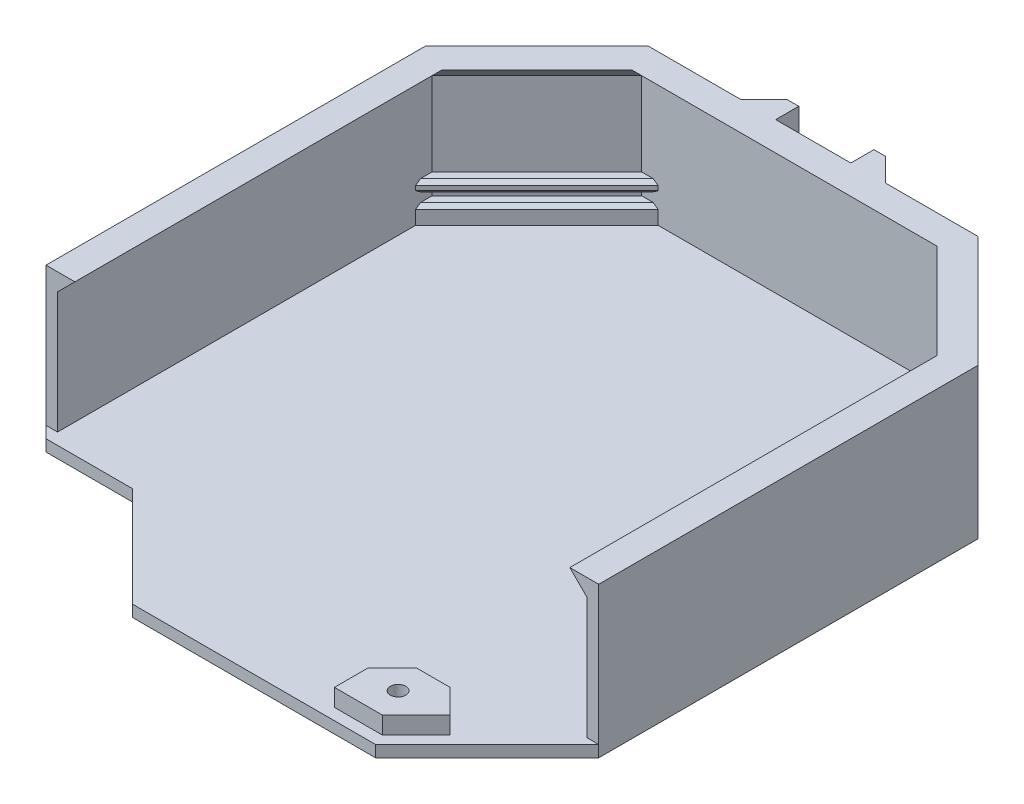
SolidWorks part; units mm, degrees
ref_plane "Front Plane" through (0, 0, 0) normal (0, 0, 1) x (1, 0, 0)
ref_plane "Top Plane" through (0, 0, 0) normal (0, 1, 0) x (1, 0, 0)
ref_plane "Right Plane" through (0, 0, 0) normal (1, 0, 0) x (0, 0, -1)
sketch "Sketch1" plane through (0, 0, 0) normal (0, 1, 0) x (1, 0, 0)
  line L2 (-1000, 0) -> (49000, 0) construction
  line L3 (0, -993.9005) -> (0, 49006.0995) construction
  line L6 (-36.195, 66.167) -> (36.195, 66.167)
  line L7 (36.195, 66.167) -> (60.706, 41.656)
  line L8 (60.706, 41.656) -> (60.706, -41.656)
  line L9 (-60.706, 41.656) -> (-60.706, -41.656)
  line L10 (-36.195, 66.167) -> (-60.706, 41.656)
  line L11 (-36.195, -66.167) -> (-60.706, -41.656)
  line L12 (-36.195, -66.167) -> (36.195, -66.167)
  line L13 (36.195, -66.167) -> (60.706, -41.656)
  point P13 (0, 66.167)
  point P14 (-60.706, 0)
  point P17 (60.706, 0)
  dimension "D1" = 132.334
  dimension "D2" = 121.412
  dimension "D3" = 135
  dimension "D4" = 41.656
extrude "Boss-Extrude1" add sketch "Sketch1" along normal blind 2.54
sketch "Sketch5" plane through (0, 2.54, 0) normal (0, 1, 0) x (1, 0, 0)
  line L0 (60.706, -41.656) -> (60.706, 41.656) construction
  line L1 (60.706, 41.656) -> (36.195, 66.167) construction
  line L2 (36.195, 66.167) -> (-36.195, 66.167) construction
  line L3 (-36.195, 66.167) -> (-60.706, 41.656) construction
  line L4 (-60.706, 41.656) -> (-60.706, -41.656) construction
  line L5 (60.706, -41.656) -> (60.706, 41.656)
  line L6 (60.706, 41.656) -> (36.195, 66.167)
  line L7 (36.195, 66.167) -> (-36.195, 66.167)
  line L8 (-36.195, 66.167) -> (-60.706, 41.656)
  line L9 (-60.706, 41.656) -> (-60.706, -41.656)
  line L10 (58.166, -41.656) -> (58.166, 40.6039)
  line L11 (58.166, 40.6039) -> (35.1429, 63.627)
  line L12 (35.1429, 63.627) -> (-35.1429, 63.627)
  line L13 (-35.1429, 63.627) -> (-58.166, 40.6039)
  line L14 (-58.166, 40.6039) -> (-58.166, -41.656)
  line L15 (-60.706, -41.656) -> (-58.166, -41.656)
  line L16 (58.166, -41.656) -> (60.706, -41.656)
  dimension "D1" = 2.54
extrude "Boss-Extrude2" add sketch "Sketch5" along normal blind 30.48
sketch "Sketch8" plane through (0, 2.54, 0) normal (0, 1, 0) x (1, 0, 0)
  line L0 (-58.166, -44.196) -> (-36.195, -66.167)
  line L1 (-60.706, -41.656) -> (-36.195, -66.167) construction
  line L2 (-36.195, -66.167) -> (-17.145, -66.167)
  line L3 (-36.195, -66.167) -> (36.195, -66.167) construction
  line L4 (-17.145, -66.167) -> (-39.116, -44.196)
  line L5 (-39.116, -44.196) -> (-58.166, -44.196)
  line L6 (-60.706, -41.656) -> (-58.166, -41.656) construction
  dimension "D1" = 2.54
  dimension "D2" = 19.05
extrude "Cut-Extrude2" cut sketch "Sketch8" against normal through all
ref_plane "PCB Bottom" through (0, 6.35, 0) normal (0, 1, 0) x (1, 0, 0)
ref_plane "PCB Top (With Tolerance)" through (0, 8.35, 0) normal (0, 1, 0) x (1, 0, 0)
sketch "Sketch9" plane through (0, 6.35, 0) normal (0, 1, 0) x (1, 0, 0)
  line L0 (-58.166, 40.6039) -> (-35.1429, 63.627)
  line L1 (-35.1429, 63.627) -> (-31.5508, 63.627)
  line L2 (-35.1429, 63.627) -> (35.1429, 63.627) construction
  line L3 (-31.5508, 63.627) -> (-58.166, 37.0118)
  line L4 (-58.166, -41.656) -> (-58.166, 40.6039) construction
  line L5 (-58.166, 37.0118) -> (-58.166, 40.6039)
  line L8 (0, -1000) -> (0, 49000) construction
  line L9 (31.5508, 63.627) -> (58.166, 37.0118)
  line L10 (35.1429, 63.627) -> (31.5508, 63.627)
  line L11 (58.166, 40.6039) -> (35.1429, 63.627)
  line L12 (58.166, 37.0118) -> (58.166, 40.6039)
  dimension "D1" = 2.54
extrude "Boss-Extrude4" add sketch "Sketch9" against normal up to surface (3.81 mm away) up to face at (-6.5193, 2.54, 14.9074)
extrude "Boss-Extrude5" add sketch "Sketch9<3>" along normal blind 2.54 from surface starting at plane "PCB Top (With Tolerance)"
sketch "Sketch9<3>" plane through (0, 6.35, 0) normal (0, 1, 0) x (1, 0, 0) same geometry as "Sketch9"
chamfer "Chamfer4" distance 0.762 angle 45 6 edges at (44.8584, 8.35, -50.3194) (44.8584, 6.35, -50.3194) (-44.8584, 6.35, -50.3194) (-44.8584, 8.35, -50.3194) (44.8584, 10.89, -50.3194) (-44.8584, 10.89, -50.3194)
sketch "Sketch10" plane through (0, 2.54, 0) normal (0, 1, 0) x (1, 0, 0)
  line L0 (42.5824, -56.1875) -> (35.1429, -63.627)
  line L1 (35.1429, -63.627) -> (24.6219, -63.627)
  line L3 (24.6219, -63.627) -> (24.6219, -56.1875)
  line L4 (24.6219, -56.1875) -> (29.8824, -50.927)
  line L5 (-17.145, -63.627) -> (35.1429, -63.627)
  line L6 (35.1429, -63.627) -> (58.9099, -39.8599)
  line L7 (-17.145, -63.627) -> (35.1429, -63.627) construction
  line L8 (35.1429, -63.627) -> (58.9099, -39.8599) construction
  line L9 (29.8824, -50.927) -> (37.3219, -50.927)
  line L10 (37.3219, -50.927) -> (42.5824, -56.1875)
  dimension "D2" = 12.7
  dimension "D1" = 2.54
extrude "Boss-Extrude6" add sketch "Sketch10" along normal up to surface (3.81 mm away) up to plane "PCB Bottom"
sketch "Sketch11" plane through (0, 6.35, 0) normal (0, 1, 0) x (1, 0, 0)
  line L0 (-17.145, -66.167) -> (36.195, -66.167) construction
  line L1 (-60.706, 41.656) -> (-60.706, -41.656) construction
  point P0 (32.258, -57.277)
  dimension "D1" = 8.89
  dimension "D2" = 92.964
hole_wizard "M3 Clearance Hole1" positions "Sketch11" profile "Sketch12" hole size "M3" standard "ANSI Metric" end condition through all
sketch "Sketch12" plane through (32.258, 6.35, 57.277) normal (1, 0, 0) x (0, 0, 1)
  line L0 (0, 0) -> (0, 6.35)
  line L1 (0, 6.35) -> (1.7, 6.35)
  line L2 (1.7, 6.35) -> (1.7, 0)
  line L5 (1.7, 0) -> (0, 0)
  line L11 (0, -6.35) -> (0, 107.95) construction
  dimension "Thru Hole Dia." = 3.4
  dimension "Thru Hole Depth" = 6.35
sketch "Sketch13" plane through (0, 0, 0) normal (0, -1, 0) x (1, 0, 0)
  circle A0 centre (32.258, 57.277) radius 4.445
  dimension "D1" = 8.89
extrude "Cut-Extrude3" cut sketch "Sketch13" against normal blind 2.032
sketch "PCB Outline" plane through (0, 6.35, 0) normal (0, 1, 0) x (1, 0, 0)
  line L7 (-15.3489, -64.3709) -> (-38.0639, -41.656)
  line L8 (-38.0639, -41.656) -> (-58.166, -41.656)
  line L9 (-15.3489, -64.3709) -> (-38.0639, -41.656) construction
  line L10 (-38.0639, -41.656) -> (-58.166, -41.656) construction
  line L36 (-57.15, -36.195) -> (-57.15, 41.529)
  line L38 (-57.15, 41.529) -> (-35.814, 62.865)
  line L40 (-35.814, 62.865) -> (35.814, 62.865)
  line L42 (35.814, 62.865) -> (57.15, 41.529)
  line L44 (57.15, 41.529) -> (57.15, -40.005)
  line L45 (57.15, -40.005) -> (34.29, -62.865)
  line L46 (34.29, -62.865) -> (-15.24, -62.865)
  line L47 (-15.24, -62.865) -> (-38.1, -40.005)
  line L48 (-38.1, -40.005) -> (-53.34, -40.005)
  line L49 (-53.34, -40.005) -> (-57.15, -36.195)
  line L58 (-58.166, -41.656) -> (-58.166, 40.6039) construction
  line L59 (24.6219, -63.627) -> (35.1429, -63.627) construction
  circle A0 centre (32.258, -57.277) radius 1.651
  point P20 (-57.15, -62.865)
  dimension "D13" = 3.302
  dimension "D1" = 1.016
  dimension "D2" = 0.762
  dimension "D3" = 125.73
  dimension "D4" = 114.3
  dimension "D5" = 91.44
  dimension "D6" = 104.394
  dimension "D7" = 135
  dimension "D8" = 135
  dimension "D9" = 2.54
  dimension "D10" = 41.91
  dimension "D11" = 22.86
  dimension "D12" = 3.81
  dimension "D14" = 19.05
  dimension "D15" = 26.67
  dimension "D16" = 21.336
  dimension "D17" = 92.964
  dimension "D18" = 22.86
  dimension "D19" = 104.394
  dimension "D20" = 89.408
  dimension "D21" = 5.588
sketch "Sketch7" plane through (0, 33.02, 0) normal (0, 1, 0) x (1, 0, 0)
  line L0 (58.166, 40.6039) -> (58.166, -41.656) construction
  line L3 (-58.166, -41.656) -> (-54.356, -41.656)
  line L10 (35.1429, 63.627) -> (58.166, 40.6039) construction
  line L11 (-35.1429, 63.627) -> (35.1429, 63.627) construction
  line L12 (-58.166, 40.6039) -> (-35.1429, 63.627) construction
  line L14 (58.166, 40.6039) -> (58.166, -41.656)
  line L15 (35.1429, 63.627) -> (58.166, 40.6039)
  line L16 (-35.1429, 63.627) -> (35.1429, 63.627)
  line L17 (-58.166, 40.6039) -> (-35.1429, 63.627)
  line L18 (-58.166, -41.656) -> (-58.166, 40.6039)
  line L19 (-54.356, -41.656) -> (-54.356, 39.0257)
  line L20 (-54.356, 39.0257) -> (-33.5647, 59.817)
  line L21 (-33.5647, 59.817) -> (33.5647, 59.817)
  line L22 (33.5647, 59.817) -> (54.356, 39.0257)
  line L23 (54.356, 39.0257) -> (54.356, -41.656)
  line L24 (54.356, -41.656) -> (58.166, -41.656)
  line L26 (-58.166, -41.656) -> (-58.166, 40.6039) construction
  dimension "D1" = 3.81
extrude "Boss-Extrude3" add sketch "Sketch7" against normal blind 3.81
chamfer "Chamfer2" distance 3.81 angle 45 5 edges at (54.356, 29.21, 1.3151) (43.9604, 29.21, -49.4214) (0, 29.21, -59.817) (-43.9604, 29.21, -49.4214) (-54.356, 29.21, 1.3151)
sketch "Sketch14" plane through (0, 0, 0) normal (0, -1, 0) x (1, 0, 0)
  line L0 (0, -1000) -> (0, 49000) construction
  line L8 (-8.255, -66.167) -> (-8.255, -71.247)
  line L9 (36.195, -66.167) -> (-36.195, -66.167) construction
  line L10 (-8.255, -71.247) -> (-10.795, -71.247)
  line L11 (-10.795, -71.247) -> (-15.875, -66.167)
  line L12 (-15.875, -66.167) -> (-8.255, -66.167)
  line L13 (10.795, -71.247) -> (15.875, -66.167)
  line L14 (8.255, -71.247) -> (10.795, -71.247)
  line L15 (8.255, -66.167) -> (8.255, -71.247)
  line L16 (15.875, -66.167) -> (8.255, -66.167)
  dimension "D1" = 16.51
  dimension "D2" = 45
  dimension "D3" = 5.08
  dimension "D4" = 2.54
extrude "Boss-Extrude10" add sketch "Sketch14" against normal up to surface (33.02 mm away) up to face at (0, 33.02, -20.559)
